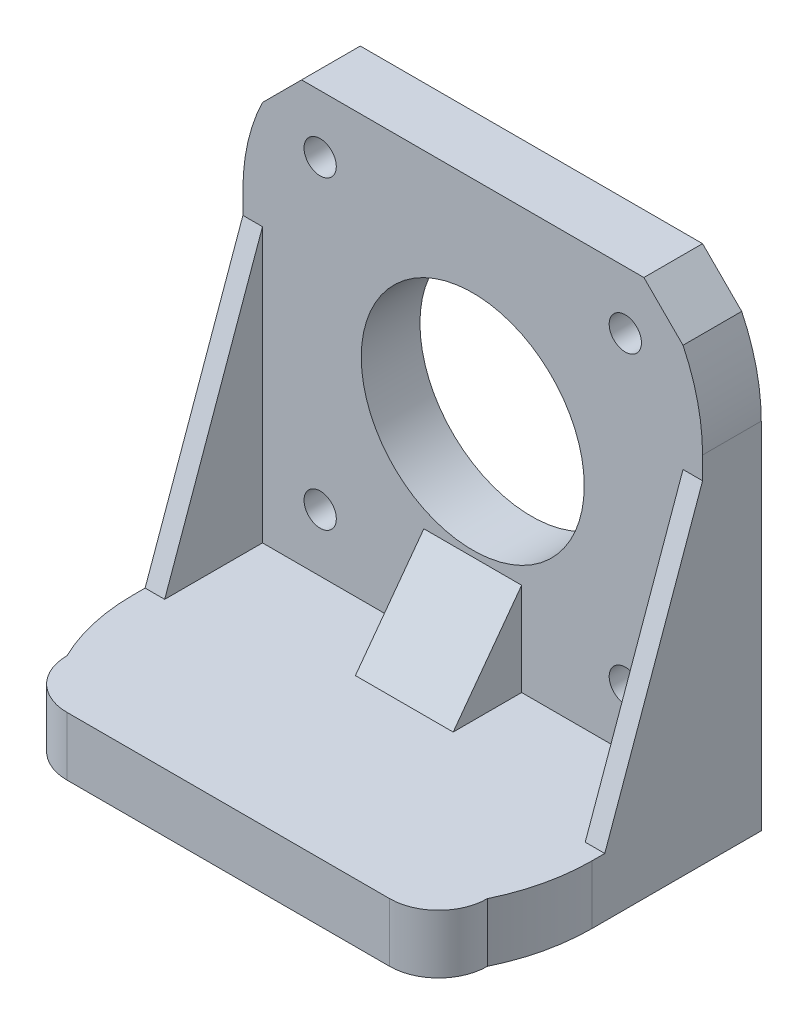
SolidWorks part; units mm, degrees
ref_plane "Alzado" through (0, 0, 0) normal (0, 0, 1) x (1, 0, 0)
ref_plane "Planta" through (0, 0, 0) normal (0, 1, 0) x (1, 0, 0)
ref_plane "Vista lateral" through (0, 0, 0) normal (1, 0, 0) x (0, 0, -1)
sketch "Croquis1" plane through (0, 0, 0) normal (0, 0, 1) x (1, 0, 0)
  line L0 (-36.8913, 0) -> (34.1697, 0) construction
  line L1 (-21.5, -21.5) -> (21.5, -21.5)
  line L2 (-21.5, -21.5) -> (-21.5, 17.5)
  line L3 (-17.5, 21.5) -> (17.5, 21.5)
  line L4 (21.5, -21.5) -> (21.5, 17.5)
  line L5 (-21.5, -21.5) -> (21.5, 21.5) construction
  line L6 (-21.5, 21.5) -> (21.5, -21.5) construction
  line L7 (0, 24.3528) -> (0, -30.5737) construction
  line L8 (-21.5, 17.5) -> (-17.5, 21.5)
  line L9 (17.5, 21.5) -> (21.5, 17.5)
  circle A0 centre (-15.6, 15.6) radius 1.65
  circle A1 centre (-15.6, -15.6) radius 1.65
  circle A2 centre (15.6, -15.6) radius 1.65
  circle A3 centre (15.6, 15.6) radius 1.65
  circle A4 centre (0, 0) radius 11.4
  point P0 (0, 0)
  dimension "D5" = 3.3
  dimension "D6" = 22.8
  dimension "D1" = 43
  dimension "D2" = 43
  dimension "D3" = 15.6
  dimension "D4" = 15.6
extrude "Saliente-Extruir1" add sketch "Croquis1" along normal blind 6
sketch "Croquis2" plane through (0, -21.5, 0) normal (0, -1, 0) x (1, 0, 0)
  line L0 (21.5, 6) -> (21.5, 0) construction
  line L1 (-21.5, 0) -> (21.5, 0)
  line L2 (-21.5, 0) -> (-21.5, 26)
  line L3 (-16.5, 31) -> (16.5, 31)
  line L4 (21.5, 0) -> (21.5, 26)
  arc A0 (16.5, 31) -> (21.5, 26) centre (16.5, 26) cw
  arc A1 (-21.5, 26) -> (-16.5, 31) centre (-16.5, 26) cw
  point P11 (-21.5, 31)
  dimension "D2" = 5
  dimension "D1" = 31
extrude "Saliente-Extruir2" add sketch "Croquis2" along normal blind 6
sketch "Croquis3" plane through (0, 0, 0) normal (1, 0, 0) x (0, 0, -1)
  line L0 (-6, -12) -> (-13, -21.5)
  line L1 (-6, -21.5) -> (-6, 17.5) construction
  line L2 (-6, -21.5) -> (-26, -21.5) construction
  line L3 (-31, -27.5) -> (-31, -21.5) construction
  dimension "D1" = 18
  dimension "D2" = 9.5
rib "Nervio1" sketch "Croquis3" sketch "Croquis3" thickness 10 extrusion direction parallel to sketch draft on no parameters "D1"=10
sketch "Croquis4" plane through (21.5, 0, 0) normal (1, 0, 0) x (0, 0, -1)
  line L0 (-6, 6.5) -> (-16, -21.5)
  line L1 (-16, -21.5) -> (-6, -21.5)
  line L6 (0, -27.5) -> (0, 17.5)
  line L7 (0, 17.5) -> (-6, 17.5)
  line L8 (-6, 17.5) -> (-6, -21.5)
  line L9 (-6, -21.5) -> (-26, -21.5)
  line L10 (-26, -21.5) -> (-26, -27.5)
  line L11 (-26, -27.5) -> (0, -27.5)
  line L12 (0, -27.5) -> (0, 17.5)
  line L13 (0, 17.5) -> (-6, 17.5)
  line L14 (-6, 17.5) -> (-6, -21.5)
  line L15 (-6, -21.5) -> (-26, -21.5)
  line L16 (-26, -21.5) -> (-26, -27.5)
  line L17 (-26, -27.5) -> (0, -27.5)
  line M8 (0, -27.5) -> (0, 17.5)
  line M9 (0, 17.5) -> (-6, 17.5)
  line M10 (-6, 17.5) -> (-6, -21.5)
  line M11 (-6, -21.5) -> (-26, -21.5)
  line M12 (-26, -21.5) -> (-26, -27.5)
  line M13 (-26, -27.5) -> (0, -27.5)
  dimension "D2" = 28
  dimension "D1" = 0
extrude "Saliente-Extruir3" add sketch "Croquis4" along normal blind 2 contours L0 M10 M11 | M13 M8 M9 M10 M11 M12 region at (21.5, -12.1667, 9.3333) region at (21.5, 12, 5.4803)
fillet "Redondeo1" radius 20 2 edges at (23.5, 17.5, 3) (23.5, -24.5, 26)
mirror "Simetría1" about plane through (0, 0, 0) normal (1, 0, 0) of "Redondeo1", "Saliente-Extruir3"
